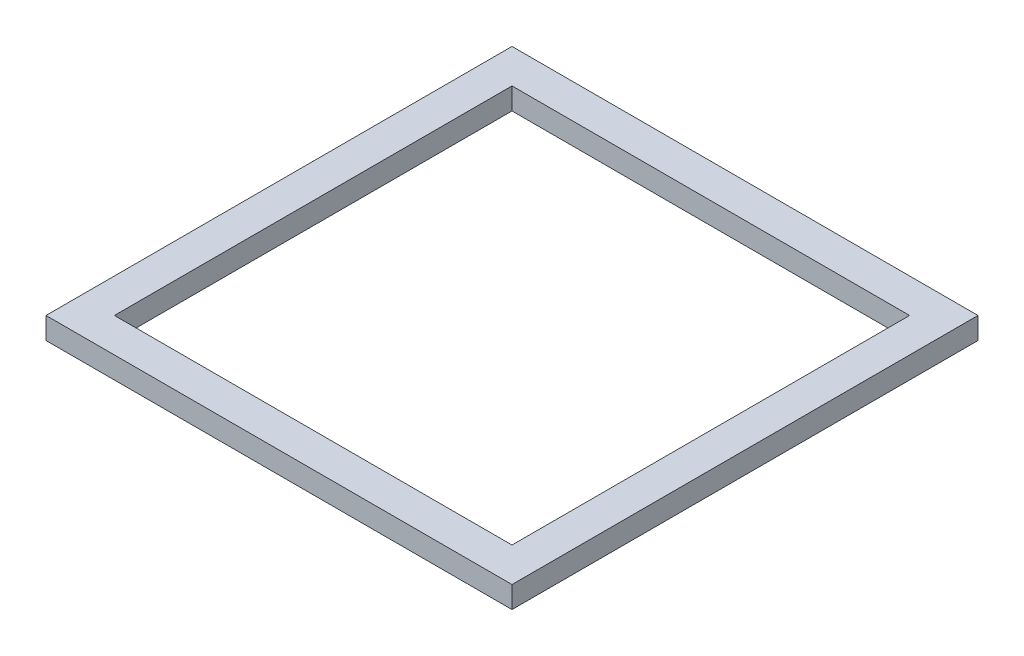
SolidWorks part; units mm, degrees
ref_plane "Front Plane" through (0, 0, 0) normal (0, 0, 1) x (1, 0, 0)
ref_plane "Top Plane" through (0, 0, 0) normal (0, 1, 0) x (1, 0, 0)
ref_plane "Right Plane" through (0, 0, 0) normal (1, 0, 0) x (0, 0, -1)
sketch "Sketch1" plane through (0, 0, 0) normal (0, 1, 0) x (1, 0, 0)
  line L1 (-136.25, 136.25) -> (136.25, 136.25)
  line L2 (-136.25, 136.25) -> (-136.25, -136.25)
  line L3 (-136.25, -136.25) -> (136.25, -136.25)
  line L4 (136.25, 136.25) -> (136.25, -136.25)
  line L5 (-136.25, 136.25) -> (136.25, -136.25) construction
  line L6 (-136.25, -136.25) -> (136.25, 136.25) construction
  point P0 (0, 0)
  dimension "D1" = 272.5
extrude "Boss-Extrude1" add sketch "Sketch1" along normal blind 12.7
sketch "Sketch2" plane through (0, 12.7, 0) normal (0, 1, 0) x (1, 0, 0)
  line L0 (136.25, 136.25) -> (-136.25, 136.25) construction
  line L1 (-116.25, 116.25) -> (116.25, 116.25)
  line L2 (-116.25, 116.25) -> (-116.25, -116.25)
  line L3 (-116.25, -116.25) -> (116.25, -116.25)
  line L4 (116.25, 116.25) -> (116.25, -116.25)
  line L5 (-116.25, 116.25) -> (116.25, -116.25) construction
  line L6 (-116.25, -116.25) -> (116.25, 116.25) construction
  line L7 (136.25, -136.25) -> (136.25, 136.25) construction
  point P0 (0, 0)
  dimension "D1" = 20
  dimension "D2" = 20
extrude "Cut-Extrude1" cut sketch "Sketch2" against normal blind 12.7
